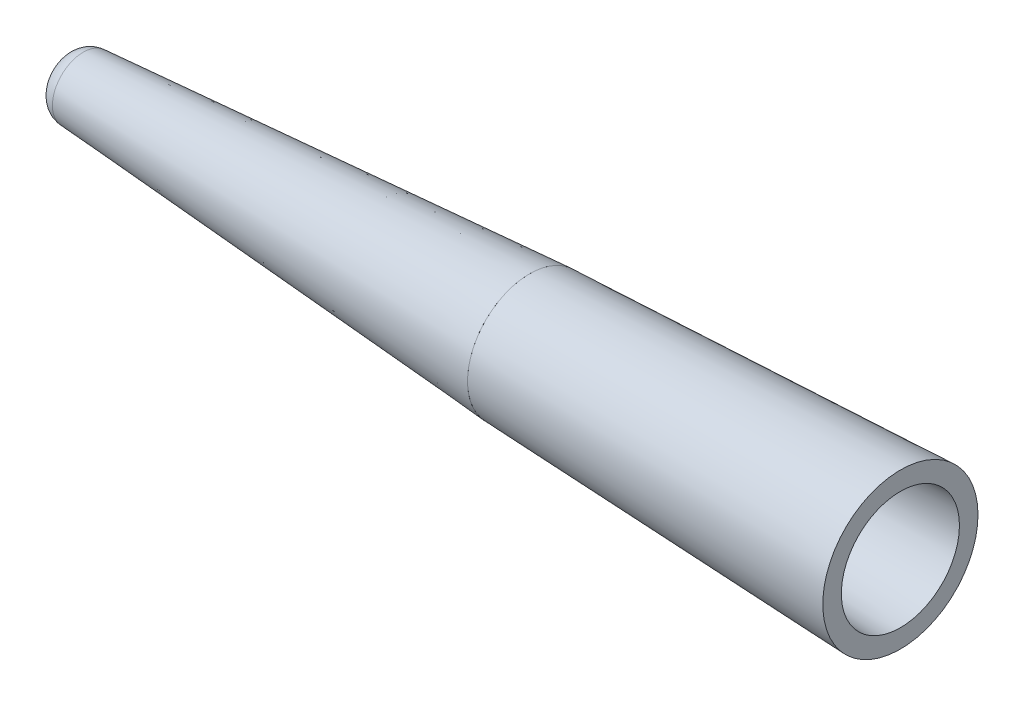
SolidWorks part; units mm, degrees
note: '?' marks a value the reader was unsure of.
ref_plane "Front Plane" through (0, 0, 0) normal (0, 0, 1) x (1, 0, 0)
ref_plane "Top Plane" through (0, 0, 0) normal (0, 1, 0) x (1, 0, 0)
ref_plane "Right Plane" through (0, 0, 0) normal (1, 0, 0) x (0, 0, -1)
sketch "Sketch2" plane through (0, 0, 0) normal (0, 0, 1) x (1, 0, 0)
  line L0 (-19.2758, 0) -> (50, 0) construction
  line L1 (0, 21.4747) -> (0, -15.9358) construction
  line L2 (0, 1.2) -> (54.9325, 5.0413) construction
  line L3 (0, 3.2) -> (55.9028, 7.1091) construction
  line L4 (0, 1.2) -> (50, 4.6963)
  line L5 (1.8511, 3.3294) -> (50, 6.6963)
  line L6 (50, 0) -> (50, 20.2328) construction
  line L7 (50, 6.6963) -> (50, 4.6963)
  arc A0 (0, 1.2) -> (1.8511, 3.3294) centre (1.9903, 1.3392) cw
  dimension "D1" = 4
  dimension "D2" = 1.2
  dimension "D3" = 2
  dimension "D4" = 50
revolve "Revolve2" add sketch "Sketch2" angle 360 about L0
ref_plane "Plane1" through (50, 0, 0) normal (1, 0, 0) x (0, 0, -1)
ref_axis "Axis1" through (50, 0, 0) along (-1, 0, 0)
sketch "Sketch3" plane through (0, 0, 0) normal (0, 0, 1) x (1, 0, 0)
  line L0 (50, 6.6963) -> (180, 6.6963) construction
  line L1 (50, -7.366) -> (50, 7.366) construction
  line L2 (50, 6.6963) -> (1.8511, 3.3294) construction
  line L3 (50, 6.6963) -> (180, 12.145) construction
  line L4 (50, 4.6946) -> (180, 10.1432)
  line L5 (180, 10.1432) -> (180, 12.145)
  line L6 (180, 12.145) -> (50, 6.6963)
  line L7 (50, 6.6963) -> (50, 4.6946)
  dimension "D1" = 2.4
  dimension "D2" = 130
  dimension "D3" = 2
revolve "Revolve3" add sketch "Sketch3" angle 360 about axis through (50, 0, 0) along (-1, 0, 0)
ref_plane "Plane2" through (90, 0, 0) normal (1, 0, 0) x (0, 0, -1)
ref_plane "Plane3" through (180, 0, 0) normal (1, 0, 0) x (0, 0, -1)
ref_plane "Plane4" through (0, -12.145, 0) normal (0, 1, 0) x (1, 0, 0)
ref_axis "Axis2" through (180, -12.145, -13.3595) along (0, 0, 1)?
ref_plane "Plane5" through (83.9275, 83.9275, 0) normal (-0.7071, -0.7071, 0) x (0, 0, 1)
other "SurfaceCut1" flip cut yes
